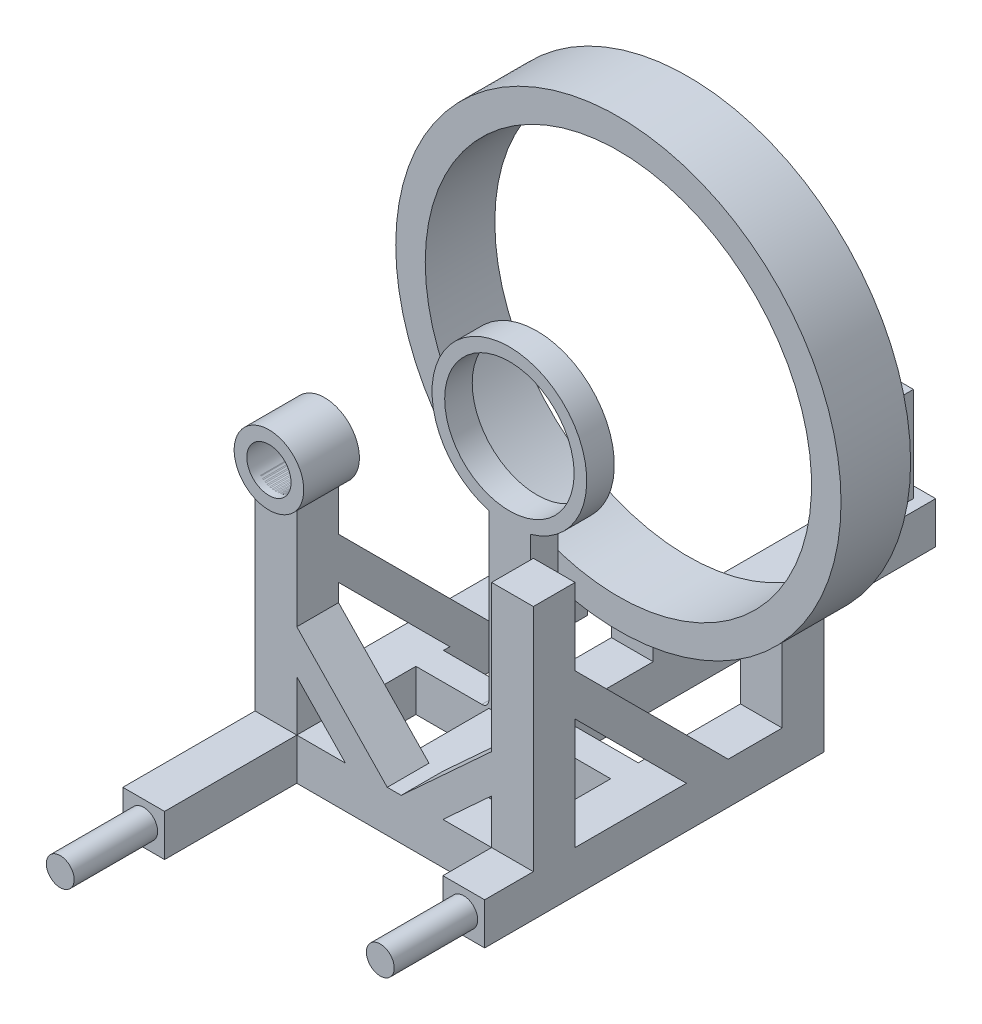
SolidWorks part; units mm, degrees
other "Markup1"
sketch "Sketch15" plane through (18.05, 14, 0) normal (0.0458, 0.1049, 0.9934) x (0.9989, -0.0157, -0.0444)
other "Markup2"
sketch "Sketch46" plane through (24.24, 35.18, 6) normal (0.2146, 0.4944, 0.8423) x (0.973, -0.1833, -0.1403)
ref_plane "Front Plane" through (0, 0, 0) normal (0, 0, 1) x (1, 0, 0)
ref_plane "Top Plane" through (0, 0, 0) normal (0, 1, 0) x (1, 0, 0)
ref_plane "Right Plane" through (0, 0, 0) normal (1, 0, 0) x (0, 0, -1)
sketch "Sketch3" plane through (0, 0, 0) normal (0, 0, 1) x (1, 0, 0)
  line L1 (-1.5, 1.5) -> (1.5, 1.5)
  line L2 (-1.5, 1.5) -> (-1.5, -1.5)
  line L3 (-1.5, -1.5) -> (1.5, -1.5)
  line L4 (1.5, 1.5) -> (1.5, -1.5)
  line L5 (-1.5, 1.5) -> (1.5, -1.5) construction
  line L6 (-1.5, -1.5) -> (1.5, 1.5) construction
  point P0 (0, 0)
  dimension "D1" = 3
  dimension "D3" = 0
  dimension "D2" = 3
  dimension "D4" = 0
sketch "Sketch4" plane through (0, 0, 0) normal (0, 1, 0) x (1, 0, 0)
  line L0 (0, 0) -> (0, 11)
  line L1 (0, 11) -> (17, 11)
  line L2 (17, 11) -> (17, 6)
  dimension "D1" = 17
  dimension "D2" = 11
  dimension "D3" = 5
sweep "Sweep3" add profiles "Sketch3" path "Sketch4"
sketch "Sketch7" plane through (0, 0, 0) normal (0, 1, 0) x (1, 0, 0)
  line L2 (-1.5, 12.5) -> (1.5, 12.5)
  line L3 (-1.5, 12.5) -> (-1.5, 9.5)
  line L4 (-1.5, 9.5) -> (1.5, 9.5)
  line L5 (1.5, 12.5) -> (1.5, 9.5)
  line L6 (-1.5, 12.5) -> (1.5, 9.5) construction
  line L7 (-1.5, 9.5) -> (1.5, 12.5) construction
  point P0 (0, 11)
  dimension "D1" = 1.5
  dimension "D2" = 3
extrude "Boss-Extrude1" add sketch "Sketch7" along normal blind 16.5
ref_plane "Plane8" through (0, 0, -11) normal (0, 0, 1) x (1, 0, 0)
sketch "Sketch12" plane through (0, 0, -11) normal (0, 0, 1) x (1, 0, 0)
  circle A1 centre (0, 17.5) radius 2.5
  dimension "D1" = 0
  dimension "D2" = 5
  dimension "D3" = 17.5
extrude "Boss-Extrude4" add sketch "Sketch12" along normal mid plane 4 separate body
ref_plane "Plane9" through (9.09, 0, 0) normal (1, 0, 0) x (0, 0, -1)
sketch "Sketch16" plane through (0, 0, -13) normal (0, 0, -1) x (-1, 0, 0)
  circle A0 centre (0, 17.5) radius 1.59
sketch "Sketch17" plane through (0, 0, 0) normal (0, 0, 1) x (1, 0, 0)
  circle A0 centre (0, 0) radius 1
  dimension "D1" = 2
extrude "Boss-Extrude5" add sketch "Sketch17" along normal blind 6
sketch "Sketch18" plane through (0, 0, -6) normal (0, 0, 1) x (1, 0, 0)
  line L0 (18.5, 1.5) -> (18.5, -1.5) construction
  line L1 (15.5, 1.5) -> (18.5, 1.5) construction
  circle A0 centre (17, 0) radius 1
  dimension "D1" = 2
  dimension "D2" = 1.5
  dimension "D3" = 1.5
extrude "Boss-Extrude6" add sketch "Sketch18" along normal blind 6
ref_plane "Plane10" through (0, 0, -12.5) normal (0, 0, 1) x (1, 0, 0)
sketch "Sketch19" plane through (0, 0, -12.5) normal (0, 0, 1) x (1, 0, 0)
  line L0 (1.5, -1.5) -> (15.5, -1.5) construction
  line L1 (6.74, 1.5) -> (9.74, 1.5)
  line L2 (6.74, 1.5) -> (6.74, -1.5)
  line L3 (6.74, -1.5) -> (9.74, -1.5)
  line L4 (9.74, 1.5) -> (9.74, -1.5)
  line L5 (6.74, 1.5) -> (9.74, -1.5) construction
  line L6 (6.74, -1.5) -> (9.74, 1.5) construction
  point P0 (8.24, 0)
  dimension "D1" = 3
  dimension "D2" = 3
  dimension "D3" = 8.24
extrude "Boss-Extrude7" add sketch "Sketch19" against normal blind 7.54 separate body
sketch "Sketch21" plane through (0, 1.5, 0) normal (0, 1, 0) x (1, 0, 0)
  line L0 (9.74, 20.04) -> (9.74, 12.5) construction
  line L1 (6.74, 20.04) -> (9.74, 20.04)
  line L2 (6.74, 20.04) -> (6.74, 18.06)
  line L3 (6.74, 18.06) -> (9.74, 18.06)
  line L4 (9.74, 20.04) -> (9.74, 18.06)
  dimension "D2" = 1.98
extrude "Boss-Extrude8" add sketch "Sketch21" along normal blind 17.68
ref_plane "Plane11" through (0, 0, -19.05) normal (0, 0, 1) x (1, 0, 0)
sketch "Sketch22" plane through (0, 0, -19.05) normal (0, 0, 1) x (1, 0, 0)
  line L0 (6.74, 1.5) -> (9.74, 1.5) construction
  circle A0 centre (8.2171, 19.18) radius 5.56
  point P4 (8.24, 1.5)
  dimension "D1" = 11.12
  dimension "D2" = 17.68
extrude "Boss-Extrude9" add sketch "Sketch22" along normal mid plane 1.98
sketch "Sketch23" plane through (0, 0, -20.04) normal (0, 0, -1) x (-1, 0, 0)
  circle A0 centre (-8.2171, 19.18) radius 4.65
extrude "Cut-Extrude2" cut sketch "Sketch23" against normal mid plane 5
sketch "Sketch24" plane through (0, 0, -20.04) normal (0, 0, -1) x (-1, 0, 0)
  line L0 (-6.74, 1.5) -> (-9.74, 1.5) construction
  line L1 (-9.74, -1.5) -> (-6.74, -1.5)
  line L2 (-9.74, -1.5) -> (-9.74, 1.5)
  line L3 (-9.74, 1.5) -> (-6.74, 1.5)
  line L4 (-6.74, -1.5) -> (-6.74, 1.5)
  line L5 (-6.74, 1.5) -> (-9.74, 1.5) construction
extrude "Boss-Extrude10" add sketch "Sketch24" along normal blind 9.83
sketch "Sketch25" plane through (0, 1.5, 0) normal (0, 1, 0) x (1, 0, 0)
  line L0 (9.74, 29.87) -> (9.74, 20.04) construction
  line L1 (6.74, 29.87) -> (9.74, 29.87)
  line L2 (6.74, 29.87) -> (6.74, 26.87)
  line L3 (6.74, 26.87) -> (9.74, 26.87)
  line L4 (9.74, 29.87) -> (9.74, 26.87)
  dimension "D1" = 3
extrude "Boss-Extrude11" add sketch "Sketch25" along normal blind 3
ref_plane "Plane12" through (0, 0, -28.37) normal (0, 0, -1) x (-1, 0, 0)
sketch "Sketch27" plane through (0, 0, -28.37) normal (0, 0, -1) x (-1, 0, 0)
  line L0 (-6.74, 1.5) -> (-9.74, 1.5) construction
  circle A0 centre (-8.24, 19.18) radius 16
  dimension "D1" = 32
  dimension "D2" = 17.68
extrude "Boss-Extrude12" add sketch "Sketch27" along normal mid plane 5
sketch "Sketch28" plane through (0, 0, -30.87) normal (0, 0, -1) x (-1, 0, 0)
  circle A0 centre (-8.24, 19.18) radius 13.88
extrude "Cut-Extrude3" cut sketch "Sketch28" against normal blind 7
sketch "Sketch31" plane through (0, 0, -29.87) normal (0, 0, -1) x (-1, 0, 0)
  line L0 (-6.74, 1.5) -> (-9.74, 1.5) construction
  line L1 (-9.74, -1.5) -> (-6.74, -1.5)
  line L2 (-9.74, -1.5) -> (-9.74, 1.5)
  line L3 (-9.74, 1.5) -> (-6.74, 1.5)
  line L4 (-6.74, -1.5) -> (-6.74, 1.5)
  line L5 (-6.74, 1.5) -> (-9.74, 1.5) construction
extrude "Boss-Extrude13" add sketch "Sketch31" along normal blind 17.3
sketch "Sketch32" plane through (0, 1.5, 0) normal (0, 1, 0) x (1, 0, 0)
  line L5 (6.74, 47.17) -> (6.74, 29.87) construction
  line L6 (7.54, 46.37) -> (8.94, 46.37)
  line L7 (7.54, 46.37) -> (7.54, 44.97)
  line L8 (7.54, 44.97) -> (8.94, 44.97)
  line L9 (8.94, 46.37) -> (8.94, 44.97)
  line L10 (7.54, 46.37) -> (8.94, 44.97) construction
  line L11 (7.54, 44.97) -> (8.94, 46.37) construction
  line L12 (6.74, 47.17) -> (9.74, 47.17) construction
  point P0 (8.24, 45.67)
  dimension "D1" = 1.4
  dimension "D2" = 1.4
  dimension "D3" = 1.5
  dimension "D4" = 1.5
extrude "Boss-Extrude14" add sketch "Sketch32" along normal blind 6.8
sketch "Sketch33" plane through (0, 0, -12.5) normal (0, 0, -1) x (-1, 0, 0)
  line L0 (1.5, -1.5) -> (-18.5, -1.5) construction
  line L1 (-18.5, 1.5) -> (-15.5, 1.5)
  line L2 (-18.5, 1.5) -> (-18.5, -1.5)
  line L3 (-18.5, -1.5) -> (-15.5, -1.5)
  line L4 (-15.5, 1.5) -> (-15.5, -1.5)
  dimension "D1" = 3
extrude "Boss-Extrude15" add sketch "Sketch33" along normal blind 17.88
sketch "Sketch34" plane through (0, 1.5, 0) normal (0, 1, 0) x (1, 0, 0)
  line L5 (15.5, 30.38) -> (18.5, 30.38) construction
  line L6 (15.5, 30.38) -> (18.5, 30.38)
  line L7 (15.5, 30.38) -> (15.5, 27.38)
  line L8 (15.5, 27.38) -> (18.5, 27.38)
  line L9 (18.5, 30.38) -> (18.5, 27.38)
  line L10 (18.5, 30.38) -> (18.5, 12.5) construction
  dimension "D1" = 3
  dimension "D2" = 3
extrude "Boss-Extrude16" add sketch "Sketch34" along normal blind 5.5
ref_plane "Plane13" through (8.5, 0, 0) normal (-1, 0, 0) x (0, 0, 1)
sketch "Sketch36" plane through (0, 1.5, 0) normal (0, 1, 0) x (1, 0, 0)
  line L0 (1.5, 12.5) -> (18.5, 12.5) construction
  line L1 (5, 12.5) -> (8, 12.5)
  line L2 (5, 12.5) -> (5, 9.5)
  line L3 (5, 9.5) -> (8, 9.5)
  line L4 (8, 12.5) -> (8, 9.5)
  line L5 (1.5, 9.5) -> (15.5, 9.5) construction
  line L6 (1.5, 9.5) -> (1.5, 12.5) construction
  point P10 (5, 11)
  dimension "D1" = 3
  dimension "D2" = 3.5
ref_plane "Plane14" through (0, 0, -11) normal (0, 0, 1) x (1, 0, 0)
sketch "Sketch39" plane through (0, 0, -11) normal (0, 0, 1) x (1, 0, 0)
  line L0 (6.5, 1.5) -> (0, 8.24)
  line L1 (0, 0) -> (0, 8.2619) construction
  line L7 (5, 1.5) -> (8, 1.5) construction
  dimension "D1" = 8.24
  dimension "D2" = 6.5
sweep "Sweep4" add profiles "Sketch36" path "Sketch39"
extrude "Cut-Extrude7" cut sketch "Sketch16" against normal mid plane 10
sketch "Sketch41" plane through (0, 0, -12.5) normal (0, 0, -1) x (-1, 0, 0)
  line L1 (1.5, -1.5) -> (-1.5, -1.5)
  line L2 (1.5, -1.5) -> (1.5, 1.5)
  line L3 (1.5, 1.5) -> (-1.5, 1.5)
  line L4 (-1.5, -1.5) -> (-1.5, 1.5)
  dimension "D1" = 3
extrude "Boss-Extrude17" add sketch "Sketch41" along normal blind 17.88
sketch "Sketch42" plane through (0, 1.5, 0) normal (0, 1, 0) x (1, 0, 0)
  line L0 (1.5, 30.38) -> (1.5, 12.5) construction
  line L1 (-1.5, 30.38) -> (1.5, 30.38)
  line L2 (-1.5, 30.38) -> (-1.5, 27.38)
  line L3 (-1.5, 27.38) -> (1.5, 27.38)
  line L4 (1.5, 30.38) -> (1.5, 27.38)
  dimension "D1" = 3
extrude "Boss-Extrude18" add sketch "Sketch42" along normal blind 5
sketch "Sketch43" plane through (0, 1.5, 0) normal (0, 1, 0) x (1, 0, 0)
  line L1 (15.5, 9.5) -> (18.5, 9.5)
  line L2 (15.5, 9.5) -> (15.5, 12.5)
  line L3 (15.5, 12.5) -> (18.5, 12.5)
  line L4 (18.5, 9.5) -> (18.5, 12.5)
extrude "Boss-Extrude19" add sketch "Sketch43" along normal blind 16.5
sketch "Sketch47" plane through (0, 1.5, 0) normal (0, 1, 0) x (1, 0, 0)
  line L0 (9.74, 12.5) -> (15.5, 12.5) construction
  line L1 (9, 12.5) -> (12, 12.5)
  line L2 (9, 12.5) -> (9, 9.5)
  line L3 (9, 9.5) -> (12, 9.5)
  line L4 (12, 12.5) -> (12, 9.5)
  line L5 (8, 9.5) -> (15.5, 9.5) construction
  line L6 (15.5, 12.5) -> (15.5, 9.5) construction
  dimension "D1" = 3
  dimension "D2" = 3.5
sketch "Sketch51" plane through (0, 0, -11) normal (0, 0, 1) x (1, 0, 0)
  line L0 (17, 0) -> (17, 9.292) construction
  line L1 (10.5, 1.5) -> (17, 7.472)
  line L3 (9, 1.5) -> (12, 1.5) construction
sweep "Sweep5" add profiles "Sketch47" path "Sketch51"
ref_plane "Plane15" through (0, 0, -12.5) normal (0, 0, 1) x (1, 0, 0)
sketch "Sketch53" plane through (0, 0, -12.5) normal (0, 0, 1) x (1, 0, 0)
  line L7 (-1.5, 16.5) -> (-1.5, 1.5) construction
  line L8 (-1.5, 12.5) -> (1.5, 12.5)
  line L9 (-1.5, 12.5) -> (-1.5, 9.5)
  line L10 (-1.5, 9.5) -> (1.5, 9.5)
  line L11 (1.5, 12.5) -> (1.5, 9.5)
  line L12 (1.5, 16.5) -> (1.5, 8.24) construction
  point P8 (-1.5, 11)
  dimension "D1" = 3
  dimension "D2" = 11
sketch "Sketch54" plane through (-1.5, 0, 0) normal (-1, 0, 0) x (0, 0, 1)
  line L0 (-12.5, 11) -> (-23.5, 0)
  line L1 (-12.5, 12.5) -> (-12.5, 9.5) construction
  line L2 (-12.5, -18.7014) -> (-12.5, 18.7014) construction
  dimension "D1" = 11
sweep "Sweep6" add profiles "Sketch53" path "Sketch54"
mirror "Mirror11" about plane through (8.5, 0, 0) normal (-1, 0, 0) of "Sweep6"
sketch "Sketch55" plane through (6.74, 0, 0) normal (-1, 0, 0) x (0, 0, 1)
  line L0 (-30.38, -1.5) -> (-12.5, -1.5) construction
  line L1 (-20.04, 1.5) -> (-18.06, 1.5)
  line L2 (-20.04, 1.5) -> (-20.04, -1.5)
  line L3 (-20.04, -1.5) -> (-18.06, -1.5)
  line L4 (-18.06, 1.5) -> (-18.06, -1.5)
extrude "Boss-Extrude20" add sketch "Sketch55" along normal up to next
sketch "Sketch56" plane through (9.74, 0, 0) normal (1, 0, 0) x (0, 0, -1)
  line L0 (20.04, 1.5) -> (18.06, 1.5) construction
  line L1 (18.06, 1.5) -> (20.04, 1.5)
  line L2 (18.06, 1.5) -> (18.06, -1.5)
  line L3 (18.06, -1.5) -> (20.04, -1.5)
  line L4 (20.04, 1.5) -> (20.04, -1.5)
  line L5 (20.5, 1.5) -> (12.5, 1.5) construction
extrude "Boss-Extrude21" add sketch "Sketch56" along normal up to next
fillet "Fillet1" radius 0.5 1 edges at (6.74, 1.5, -19.05)
fillet "Fillet2" radius 0.5 1 edges at (9.74, 1.5, -19.05)
